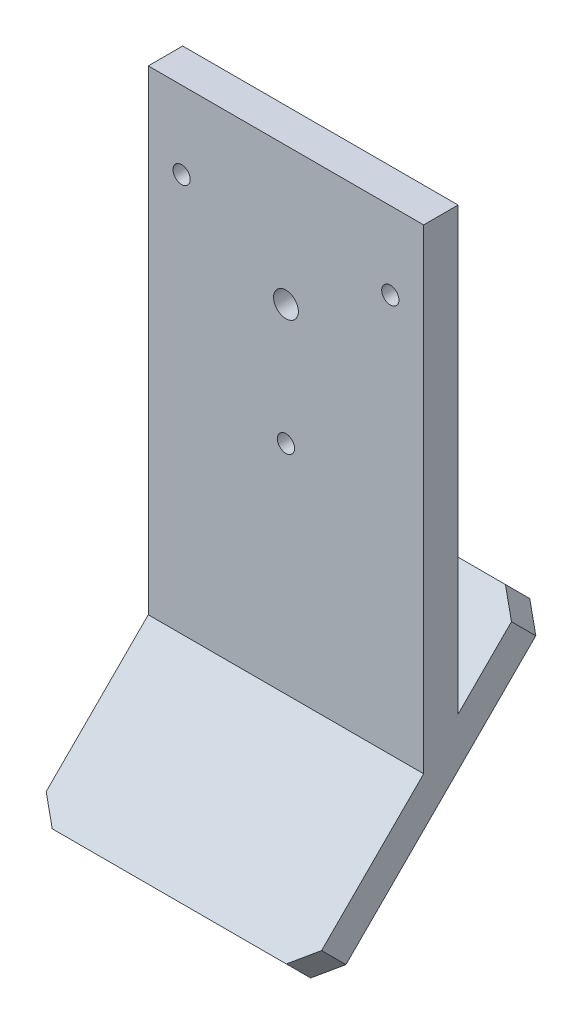
SolidWorks part; units mm, degrees
material "Polyether Polyol"
ref_plane "Front Plane" through (0, 0, 0) normal (0, 0, 1) x (1, 0, 0)
ref_plane "Top Plane" through (0, 0, 0) normal (0, 1, 0) x (1, 0, 0)
ref_plane "Right Plane" through (0, 0, 0) normal (1, 0, 0) x (0, 0, -1)
sketch "Sketch1" plane through (0, 0, 0) normal (1, 0, 0) x (0, 0, -1)
  line L0 (-15.9099, -15.9099) -> (15.9099, 15.9099)
  line L1 (15.9099, 15.9099) -> (12.3744, 19.4454)
  line L2 (12.3744, 19.4454) -> (2.5, 9.5711)
  line L3 (2.5, 9.5711) -> (2.5, 73.6134)
  line L4 (2.5, 73.6134) -> (-2.5, 73.6134)
  line L5 (-2.5, 73.6134) -> (-2.5, 4.5711)
  line L6 (-2.5, 4.5711) -> (-19.4454, -12.3744)
  line L7 (-19.4454, -12.3744) -> (-15.9099, -15.9099)
  line L8 (0, 0) -> (0, 73.6134) construction
  dimension "D1" = 45
  dimension "D2" = 45
  dimension "D3" = 5
  dimension "D4" = 5
  dimension "D5" = 54.1679
extrude "Boss-Extrude1" add sketch "Sketch1" along normal mid plane 40
hole_wizard "M3x0.5 Tapped Hole1" positions "Sketch2" profile "Sketch3" tap size "M3x0.5" standard "ANSI Metric" end condition up to next
sketch "Sketch2" plane through (0, 0, 2.5) normal (0, 0, 1) x (1, 0, 0)
  line L0 (-15.1554, 62.3634) -> (0, 53.6134) construction
  line L1 (0, 53.6134) -> (0, 36.1134) construction
  line L4 (15.1554, 62.3634) -> (0, 53.6134) construction
  line L7 (0, 53.6134) -> (-20, 53.6134) construction
  line L8 (-20, 73.6134) -> (-20, 4.5711) construction
  line L11 (0, 73.6134) -> (0, 53.6134) construction
  line L12 (20, 73.6134) -> (-20, 73.6134) construction
  circle A0 centre (0, 53.6134) radius 17.5 construction
  point P0 (-15.1554, 62.3634)
  point P2 (15.1554, 62.3634)
  point P4 (0, 36.1134)
  dimension "D2" = 35
  dimension "D1" = 120
sketch "Sketch3" plane through (-15.1554, 62.3634, 2.5) normal (1, 0, 0) x (0, -1, 0)
  line L0 (0, 0) -> (0, 5)
  line L1 (0, 5) -> (1.25, 5)
  line L2 (1.25, 5) -> (1.25, 0)
  line L5 (1.25, 0) -> (0, 0)
  line L11 (0, -6.35) -> (0, 107.95) construction
  dimension "Thru Tap Drill Dia." = 2.5
  dimension "Thru Tap Drill Depth" = 5
cosmetic thread "Hole Thread1"
cosmetic thread "Hole Thread2"
cosmetic thread "Hole Thread3"
hole_wizard "M3 Clearance Hole1" positions "Sketch4" profile "Sketch5" hole size "M3" standard "ANSI Metric" end condition up to next
sketch "Sketch4" plane through (0, 0, 2.5) normal (0, 0, 1) x (1, 0, 0)
  point P0 (0, 53.6134)
sketch "Sketch5" plane through (0, 53.6134, 2.5) normal (1, 0, 0) x (0, -1, 0)
  line L0 (0, 0) -> (0, 5)
  line L1 (0, 5) -> (1.8, 5)
  line L2 (1.8, 5) -> (1.8, 0)
  line L5 (1.8, 0) -> (0, 0)
  line L11 (0, -6.35) -> (0, 107.95) construction
  dimension "Thru Hole Dia." = 3.6
  dimension "Thru Hole Depth" = 5
chamfer "Chamfer1" distance 3 angle 45 4 edges at (20, -14.1421, 17.6777) (-20, -14.1421, 17.6777) (-20, 17.6777, -14.1421) (20, 17.6777, -14.1421)
